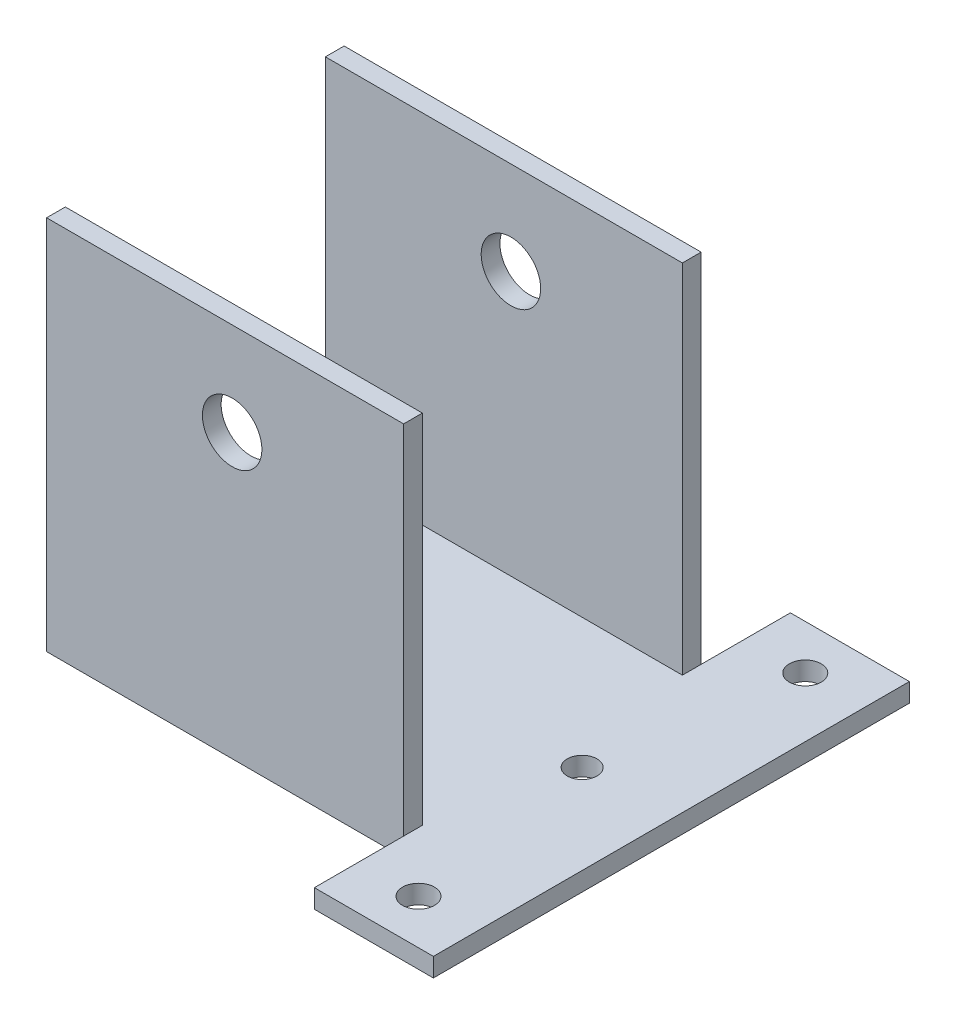
SolidWorks part; units mm, degrees
material "6061 Alloy"
ref_plane "Front Plane" through (0, 0, 0) normal (0, 0, 1) x (1, 0, 0)
ref_plane "Top Plane" through (0, 0, 0) normal (0, 1, 0) x (1, 0, 0)
ref_plane "Right Plane" through (0, 0, 0) normal (1, 0, 0) x (0, 0, -1)
sketch "Sketch1" plane through (0, 0, 0) normal (0, 1, 0) x (1, 0, 0)
  line L0 (0, 31.75) -> (38.1, 31.75)
  line L1 (38.1, 31.75) -> (38.1, 41.275)
  line L2 (38.1, 41.275) -> (50.8, 41.275)
  line L3 (50.8, 41.275) -> (50.8, -9.525)
  line L4 (50.8, -9.525) -> (38.1, -9.525)
  line L5 (38.1, -9.525) -> (38.1, 0)
  line L6 (38.1, 0) -> (0, 0)
  line L7 (0, 0) -> (0, 31.75)
  line L8 (44.45, 36.5125) -> (44.45, -4.7625) construction
  line L9 (9.525, 15.875) -> (41.275, 15.875) construction
  circle A0 centre (44.45, 36.5125) radius 1.7
  circle A1 centre (44.45, -4.7625) radius 1.7
  circle A2 centre (9.525, 15.875) radius 1.5875
  circle A3 centre (41.275, 15.875) radius 1.5875
  point P8 (0.6652, -5.3752)
  point P10 (-13.2528, 9.7708)
  point P11 (0, 0)
  point P12 (18.8814, 9.525)
  point P17 (16.1183, 15.875)
  point P18 (8.5452, 15.875)
  dimension "D5" = 3.4
  dimension "D9" = 3.175
  dimension "D1" = 50.8
  dimension "D2" = 50.8
  dimension "D3" = 12.7
  dimension "D4" = 15.875
  dimension "D6" = 41.275
  dimension "D7" = 6.35
  dimension "D8" = 9.525
  dimension "D10" = 31.75
  dimension "D11" = 9.525
  dimension "D12" = 4.7625
  dimension "D13" = 31.75
extrude "Boss-Extrude1" add sketch "Sketch1" along normal blind 2
sketch "Sketch2" plane through (0, 2, 0) normal (0, 1, 0) x (1, 0, 0)
  line L1 (0, 31.75) -> (38.1, 31.75)
  line L2 (0, 31.75) -> (0, 29.75)
  line L3 (0, 29.75) -> (38.1, 29.75)
  line L4 (38.1, 31.75) -> (38.1, 29.75)
  line L5 (0, 0) -> (38.1, 0)
  line L6 (0, 0) -> (0, 2)
  line L7 (0, 2) -> (38.1, 2)
  line L8 (38.1, 0) -> (38.1, 2)
  dimension "D1" = 2
  dimension "D2" = 2
extrude "Boss-Extrude2" add sketch "Sketch2" along normal blind 38.1
sketch "Sketch3" plane through (0, 0, 0) normal (0, 0, 1) x (1, 0, 0)
  line L1 (38.1, 2) -> (50.8, 2) construction
  line L2 (0, 40.1) -> (0, 0) construction
  circle A0 centre (19.8, 30.168) radius 3.175
  dimension "D1" = 6.35
  dimension "D2" = 28.168
  dimension "D3" = 19.8
extrude "Cut-Extrude1" cut sketch "Sketch3" against normal through all
